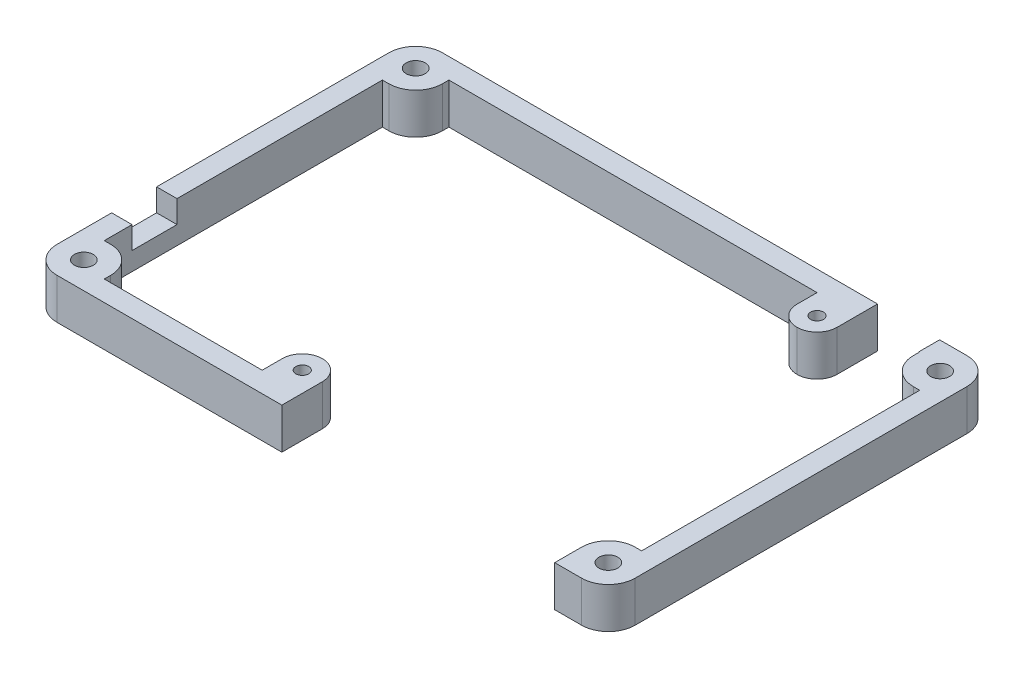
SolidWorks part; units mm, degrees
material "Rubber"
ref_plane "Front" through (0, 0, 0) normal (0, 0, 1) x (1, 0, 0)
ref_plane "Top" through (0, 0, 0) normal (0, 1, 0) x (1, 0, 0)
ref_plane "Right" through (0, 0, 0) normal (1, 0, 0) x (0, 0, -1)
sketch "Sketch1" plane through (0, 0, 0) normal (0, 1, 0) x (1, 0, 0)
  line L0 (-45, 0) -> (45, 0) construction
  line L1 (-45, 30) -> (45, 30) construction
  line L2 (-45, 30) -> (-45, -30) construction
  line L3 (-45, -30) -> (45, -30) construction
  line L4 (45, 30) -> (45, -30) construction
  line L5 (0, -30) -> (0, 30) construction
  line L6 (41.825, 26.825) -> (41.825, -26.825) construction
  line L7 (-41.825, -26.825) -> (41.825, -26.825) construction
  line L8 (-41.825, 26.825) -> (-41.825, -26.825) construction
  line L9 (-41.825, 26.825) -> (41.825, 26.825) construction
  line L10 (40.825, 25.825) -> (40.825, -25.825) construction
  line L11 (-40.825, -25.825) -> (40.825, -25.825) construction
  line L12 (-40.825, 25.825) -> (-40.825, -25.825) construction
  line L13 (-40.825, 25.825) -> (40.825, 25.825) construction
  line L14 (40.825, 21.65) -> (45, 21.65) construction
  line L15 (40.825, -21.65) -> (45, -21.65) construction
  line L16 (36.65, -25.825) -> (36.65, -30) construction
  line L17 (-36.65, -25.825) -> (-36.65, -30) construction
  line L18 (-40.825, -21.65) -> (-45, -21.65) construction
  line L19 (-36.65, 25.825) -> (-36.65, 30) construction
  line L20 (-40.825, 21.65) -> (-45, 21.65) construction
  line L21 (36.65, 25.825) -> (36.65, 30) construction
  line L22 (40.825, -25.825) -> (41.825, -25.825) construction
  circle A0 centre (-40.825, -25.825) radius 1 construction
  circle A1 centre (40.825, -25.825) radius 1 construction
  circle A2 centre (40.825, 25.825) radius 1 construction
  circle A3 centre (-40.825, 25.825) radius 1 construction
  circle A4 centre (40.825, -25.825) radius 4.175 construction
  circle A5 centre (40.825, 25.825) radius 4.175 construction
  circle A6 centre (-40.825, 25.825) radius 4.175 construction
  circle A7 centre (-40.825, -25.825) radius 4.175 construction
  dimension "D1" = 90
  dimension "D2" = 60
  dimension "D4" = 1
  dimension "D3" = 3.175
sketch "Sketch2" plane through (0, 0, 0) normal (0, 1, 0) x (1, 0, 0)
  line L0 (-45, 30) -> (-45, -30) construction
  line L1 (-45, -30) -> (45, -30) construction
  line L2 (45, 30) -> (45, -30) construction
  line L3 (-45, 30) -> (45, 30) construction
  line L4 (40.825, 21.65) -> (45, 21.65) construction
  line L5 (36.65, 25.825) -> (36.65, 30) construction
  line L6 (-36.65, 25.825) -> (-36.65, 30) construction
  line L7 (-40.825, 21.65) -> (-45, 21.65) construction
  line L8 (-36.65, -25.825) -> (-36.65, -30) construction
  line L9 (-40.825, -21.65) -> (-45, -21.65) construction
  line L10 (36.65, -25.825) -> (36.65, -30) construction
  line L11 (40.825, -21.65) -> (45, -21.65) construction
  line L16 (-45, 25.825) -> (-45, -25.825)
  line L17 (-40.825, -30) -> (40.825, -30)
  line L18 (45, 25.825) -> (45, -25.825)
  line L19 (-40.825, 30) -> (40.825, 30)
  line L20 (40.825, 21.65) -> (41.825, 21.65)
  line L21 (36.65, 25.825) -> (36.65, 26.825)
  line L22 (-36.65, 25.825) -> (-36.65, 26.825)
  line L23 (-40.825, 21.65) -> (-41.825, 21.65)
  line L24 (-36.65, -25.825) -> (-36.65, -26.825)
  line L25 (-40.825, -21.65) -> (-41.825, -21.65)
  line L26 (36.65, -25.825) -> (36.65, -26.825)
  line L27 (40.825, -21.65) -> (41.825, -21.65)
  line L28 (41.825, 26.825) -> (41.825, -26.825) construction
  line L29 (-36.65, -26.825) -> (36.65, -26.825)
  line L30 (-41.825, 26.825) -> (41.825, 26.825) construction
  line L31 (-41.825, 26.825) -> (-41.825, -26.825) construction
  line L32 (-36.65, 26.825) -> (36.65, 26.825)
  line L33 (-41.825, 21.65) -> (-41.825, -21.65)
  line L34 (41.825, 21.65) -> (41.825, -21.65)
  line L35 (-41.825, -26.825) -> (41.825, -26.825) construction
  circle A0 centre (40.825, 25.825) radius 4.175 construction
  circle A1 centre (40.825, 25.825) radius 1 construction
  circle A2 centre (-40.825, 25.825) radius 4.175 construction
  circle A3 centre (-40.825, 25.825) radius 1 construction
  circle A4 centre (-40.825, -25.825) radius 4.175 construction
  circle A5 centre (40.825, -25.825) radius 4.175 construction
  arc A6 (45, 25.825) -> (40.825, 30) centre (40.825, 25.825) ccw
  circle A7 centre (40.825, 25.825) radius 1 construction
  arc A8 (-40.825, 30) -> (-45, 25.825) centre (-40.825, 25.825) ccw
  circle A9 centre (-40.825, 25.825) radius 1 construction
  arc A10 (-36.65, -25.825) -> (-40.825, -21.65) centre (-40.825, -25.825) ccw
  arc A11 (40.825, -21.65) -> (36.65, -25.825) centre (40.825, -25.825) ccw
  circle A12 centre (-40.825, -25.825) radius 1 construction
  circle A13 centre (40.825, -25.825) radius 1 construction
  circle A14 centre (-40.825, -25.825) radius 1 construction
  circle A15 centre (40.825, -25.825) radius 1 construction
  arc A16 (-40.825, 21.65) -> (-36.65, 25.825) centre (-40.825, 25.825) ccw
  arc A17 (-45, -25.825) -> (-40.825, -30) centre (-40.825, -25.825) ccw
  arc A18 (40.825, -30) -> (45, -25.825) centre (40.825, -25.825) ccw
  arc A19 (36.65, 25.825) -> (40.825, 21.65) centre (40.825, 25.825) ccw
extrude "Boss-Extrude3" add sketch "Sketch2" along normal blind 6.35
sketch "Sketch3" plane through (0, 0, -30) normal (0, 0, -1) x (-1, 0, 0)
  line L0 (-40.825, 6.35) -> (40.825, 6.35) construction
  line L1 (-36.566, 6.35) -> (-26.9027, 6.35)
  line L2 (-36.566, 6.35) -> (-36.566, 0)
  line L3 (-36.566, 0) -> (-26.9027, 0)
  line L4 (-26.9027, 6.35) -> (-26.9027, 0)
  line L5 (-40.825, 0) -> (40.825, 0) construction
extrude "Cut-Extrude1" cut sketch "Sketch3" against normal up to vertex (3.175 mm away) up to point (36.65, 6.35, -26.825)
sketch "Sketch4" plane through (0, 0, 30) normal (0, 0, 1) x (1, 0, 0)
  line L0 (-40.825, 6.35) -> (40.825, 6.35) construction
  line L1 (36.65, 6.35) -> (-5.825, 6.35)
  line L2 (36.65, 6.35) -> (36.65, 0)
  line L3 (36.65, 0) -> (-5.825, 0)
  line L4 (-5.825, 6.35) -> (-5.825, 0)
  line L5 (-40.825, 0) -> (40.825, 0) construction
  line L6 (-40.825, 6.35) -> (-40.825, 0) construction
  dimension "D1" = 35
extrude "Cut-Extrude2" cut sketch "Sketch4" against normal up to vertex (3.175 mm away) up to point (36.65, 6.35, 26.825)
sketch "Sketch5" plane through (-45, 0, 0) normal (-1, 0, 0) x (0, 0, 1)
  line L0 (13.825, 6.35) -> (25.825, 6.35) construction
  line L1 (25.825, 6.35) -> (25.825, 0) construction
  line L3 (10.325, 9.85) -> (17.325, 9.85)
  line L4 (10.325, 9.85) -> (10.325, 2.85)
  line L5 (10.325, 2.85) -> (17.325, 2.85)
  line L6 (17.325, 9.85) -> (17.325, 2.85)
  line L7 (10.325, 9.85) -> (17.325, 2.85) construction
  line L8 (10.325, 2.85) -> (17.325, 9.85) construction
  dimension "D1" = 12
  dimension "D2" = 7
  dimension "D3" = 7
extrude "Cut-Extrude3" cut sketch "Sketch5" against normal up to surface (3.175 mm away) up to face at (-41.825, 3.175, 0)
sketch "Sketch7" plane through (0, 0, 0) normal (0, -1, 0) x (1, 0, 0)
  circle A0 centre (-40.825, -25.825) radius 1.4732
  circle A1 centre (-40.825, 25.825) radius 1.4732
  circle A2 centre (40.825, 25.825) radius 1.4732
  circle A3 centre (40.825, -25.825) radius 1.4732
  dimension "D1" = 2.9464
  dimension "D2" = 2.9464
  dimension "D3" = 2.9464
  dimension "D4" = 2.9464
extrude "Cut-Extrude4" cut sketch "Sketch7" against normal blind 10
sketch "Sketch10" plane through (0, 0, 26.825) normal (0, 0, -1) x (-1, 0, 0)
  line L0 (36.65, 0) -> (5.825, 0) construction
  line L1 (5.825, 6.35) -> (12.065, 6.35)
  line L2 (5.825, 6.35) -> (5.825, 0)
  line L3 (5.825, 0) -> (12.065, 0)
  line L4 (12.065, 6.35) -> (12.065, 0)
  dimension "D1" = 6.24
extrude "Boss-Extrude4" add sketch "Sketch10" along normal blind 6.24
sketch "Sketch11" plane through (0, 0, -26.825) normal (0, 0, 1) x (1, 0, 0)
  line L0 (26.9027, 6.35) -> (-36.65, 6.35) construction
  line L1 (26.9027, 0) -> (20.6627, 0)
  line L2 (26.9027, 0) -> (26.9027, 6.35)
  line L3 (26.9027, 6.35) -> (20.6627, 6.35)
  line L4 (20.6627, 0) -> (20.6627, 6.35)
  dimension "D1" = 6.24
extrude "Boss-Extrude5" add sketch "Sketch11" along normal blind 6.24
sketch "Sketch12" plane through (0, 6.35, 0) normal (0, 1, 0) x (1, 0, 0)
  line L0 (20.6627, 26.825) -> (26.9027, 20.585) construction
  circle A0 centre (23.7827, 23.705) radius 1
sketch "Sketch13" plane through (0, 6.35, 0) normal (0, 1, 0) x (1, 0, 0)
  line L0 (-12.065, -26.825) -> (-5.825, -20.585) construction
  circle A0 centre (-8.945, -23.705) radius 1
extrude "Cut-Extrude5" cut sketch "Sketch12" against normal through all
extrude "Cut-Extrude6" cut sketch "Sketch13" against normal through all
fillet "Fillet1" radius 3.12 4 edges at (26.9027, 3.175, -20.585) (20.6627, 3.175, -20.585) (-5.825, 3.175, 20.585) (-12.065, 3.175, 20.585)
